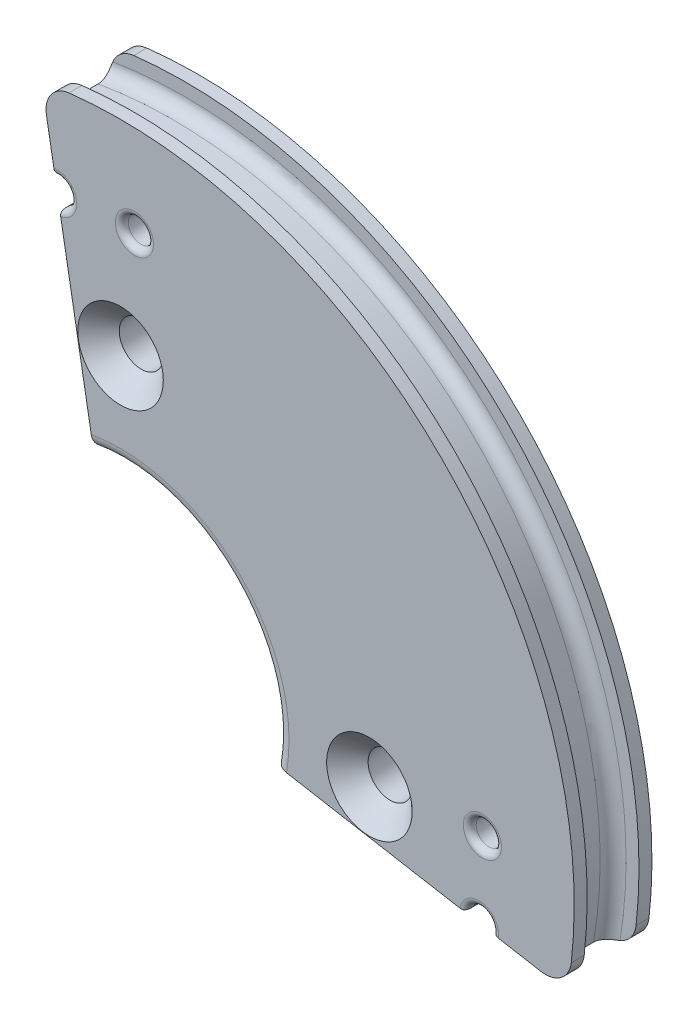
SolidWorks part; units mm, degrees
ref_plane "Front" through (0, 0, 0) normal (0, 0, 1) x (1, 0, 0)
ref_plane "Top" through (0, 0, 0) normal (0, 1, 0) x (1, 0, 0)
ref_plane "Right" through (0, 0, 0) normal (1, 0, 0) x (0, 0, -1)
sketch "Sketch1" plane through (0, 0, 0) normal (0, 0, 1) x (1, 0, 0)
  circle A2 centre (9.6, 0) radius 0.85
  circle A24 centre (0, 0) radius 17
  circle A25 centre (0, 0) radius 6
  circle A30 centre (0, -9.6) radius 0.85
  circle A32 centre (-9.6, 0) radius 0.85
  circle A34 centre (0, 9.6) radius 0.85
  point P20 (0, 0)
  dimension "D1" = 4
  dimension "D2" = 34
  dimension "D3" = 12
  dimension "D4" = 19.2
  dimension "D5" = 1.7
extrude "Boss-Extrude1" add sketch "Sketch1" along normal mid plane 3
sketch "Sketch2" plane through (0, 0, 0) normal (0, 1, 0) x (1, 0, 0)
  line L1 (0, 0) -> (0, 3.24) construction
  line L2 (17, 0) -> (19.1765, -2.75) construction
  line L3 (17, -1.5) -> (17, 1.5) construction
  line L4 (-17, 0) -> (-16.5, 0) construction
  line L5 (-17, 1.5) -> (-17, -1.5) construction
  line L6 (-16.5, -0.5) -> (-16.5, 0.5)
  line L7 (-17, 1) -> (-17, -1)
  arc A1 (-16.5, 0.5) -> (-17, 1) centre (-17, 0.5) ccw
  arc A2 (-16.5, -0.5) -> (-17, -1) centre (-17, -0.5) cw
  dimension "D1" = 33
  dimension "D2" = 2
revolve "Cut-Revolve1" cut sketch "Sketch2" angle 360 about L1
sketch "Sketch3" plane through (0, 0, 1.5) normal (0, 0, 1) x (1, 0, 0)
  line L0 (-17, 0) -> (0, 0)
  line L3 (0, 0) -> (2.952, 16.7417)
  arc A1 (-17, 0) -> (2.952, 16.7417) centre (0, 0) cw
  circle A2 centre (0, 0) radius 6 construction
  circle A3 centre (0, 0) radius 17 construction
  dimension "D4" = 100
sketch "Sketch7" plane through (0, 0, 0) normal (0, 1, 0) x (1, 0, 0)
  line L0 (1.4542, 0) -> (0, 0) construction
  line L1 (17, 1.5) -> (17.5, 1.5)
  line L2 (17, 1.5) -> (17, 1)
  line L3 (17, 1) -> (17.5, 1)
  line L4 (17.5, 1.5) -> (17.5, 1)
  line L5 (0, 0) -> (0, 3.1931) construction
  line L6 (17.5, -1.5) -> (17.5, -1)
  line L7 (17, -1) -> (17.5, -1)
  line L8 (17, -1.5) -> (17, -1)
  line L9 (17, -1.5) -> (17.5, -1.5)
  dimension "D1" = 0.5
revolve "Revolve1" add sketch "Sketch7" angle 360 about L5
sketch "Sketch4" plane through (0, 0, 0) normal (0, 0, 1) x (1, 0, 0)
  line L0 (-3.309, 18.7662) -> (0, 0)
  line L1 (0, 0) -> (12.0208, 12.0208) construction
  line L2 (0, 0) -> (-16.6927, 0) construction
  line L3 (18.7662, -3.309) -> (0, 0)
  line L5 (-3.309, 18.7662) -> (-24.9321, 18.7662)
  line L6 (-24.9321, 18.7662) -> (-24.9321, -21.7847)
  line L7 (-24.9321, -21.7847) -> (18.7662, -21.7847)
  line L10 (18.7662, -3.309) -> (18.7662, -21.7847)
  line L11 (-3.309, 18.7662) -> (18.7662, -3.309) construction
  point P0 (7.7286, 7.7286)
  dimension "D1" = 135
  dimension "D2" = 110
extrude "Cut-Extrude1" cut sketch "Sketch4" against normal through all both and the other way through all
sketch "Sketch5" plane through (0, 0, 1.5) normal (0, 0, 1) x (1, 0, 0)
  line L0 (0, 0) -> (12.3744, 12.3744) construction
  line L1 (-1.0419, 5.9088) -> (-3.0388, 17.2341) construction
  circle A0 centre (-2.4395, 13.835) radius 0.5
  circle A1 centre (0.5347, 13.9573) radius 0.4873
  arc A2 (17.2341, -3.0388) -> (-3.0388, 17.2341) centre (0, 0) ccw construction
  circle A3 centre (13.9573, 0.5347) radius 0.4873
  circle A4 centre (13.835, -2.4395) radius 0.5
  dimension "D1" = 1
extrude "Cut-Extrude2" cut sketch "Sketch5" against normal through all both and the other way through all
fillet "Fillet1" radius 0.5 2 edges at (4.2426, 4.2426, 1.5) (4.2426, 4.2426, -1.5)
chamfer "Chamfer1" distance 0.8 angle 45 2 edges at (10.45, 0, 1.5) (0.85, 9.6, 1.5)
sketch "Sketch6" plane through (0, 0, -1.5) normal (0, 0, -1) x (-1, 0, 0)
  line L0 (0, 0) -> (-12.3744, 12.3744) construction
  line L1 (-12.3744, 12.3744) -> (1.3226, 15.1171)
  line L2 (1.3226, 15.1171) -> (0, 0)
  line L3 (-12.3744, 12.3744) -> (-15.1171, -1.3226)
  line L4 (-15.1171, -1.3226) -> (0, 0)
  arc A1 (3.0388, 17.2341) -> (-17.2341, -3.0388) centre (0, 0) ccw construction
  dimension "D1" = 50
fillet "Fillet2" radius 1 2 edges at (17.2341, -3.0388, 1.25) (-3.0388, 17.2341, -1.25)
fillet "Fillet3" radius 0.25 12 edges at (-2.5263, 14.3274, 0) (-1.9471, 13.9218, 1.5) (-2.3527, 13.3426, 0) (-1.9471, 13.9218, -1.5) (13.3426, -2.3527, 0) (13.9218, -1.9471, 1.5) (14.3274, -2.5263, 0) (13.9218, -1.9471, -1.5) (13.47, 0.5347, -1.5) (14.4445, 0.5347, 1.5) (1.022, 13.9573, -1.5) (1.022, 13.9573, 1.5)
